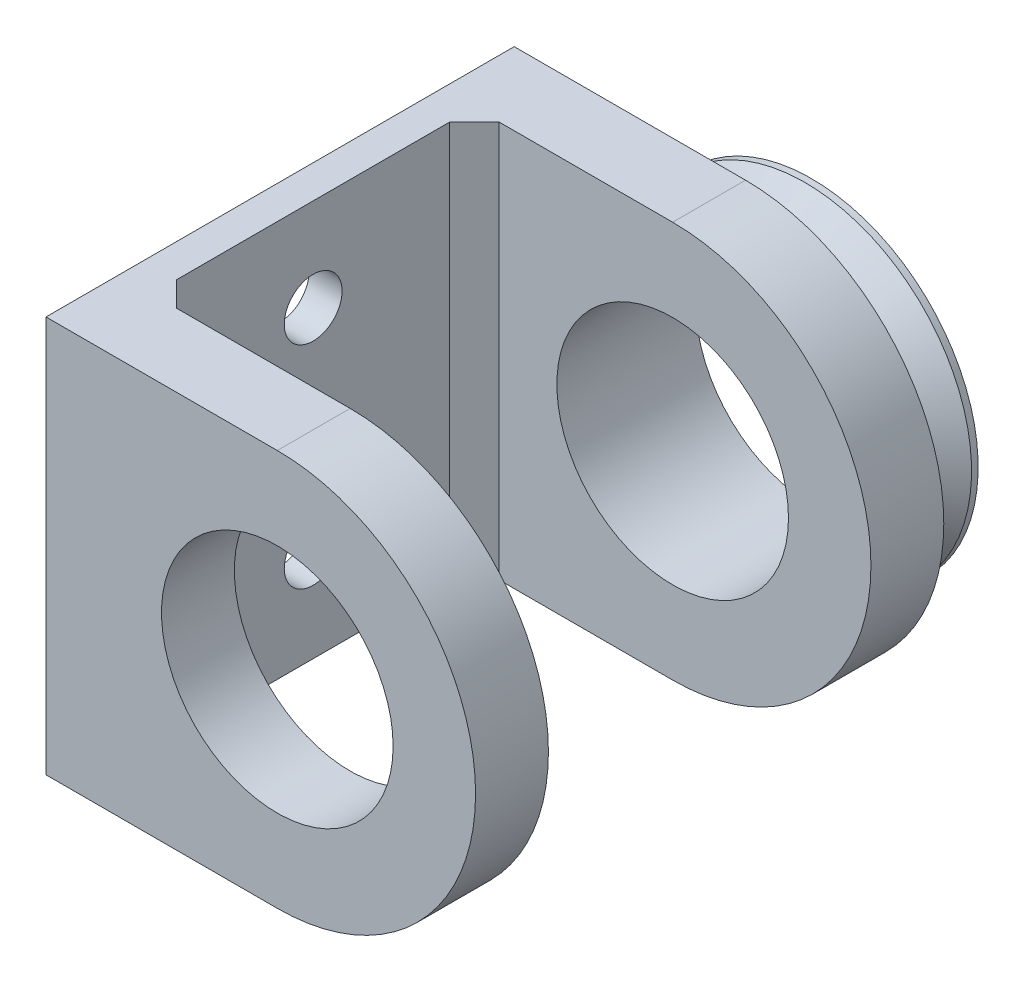
SolidWorks part; units mm, degrees
ref_plane "Front Plane" through (0, 0, 0) normal (0, 0, 1) x (1, 0, 0)
ref_plane "Top Plane" through (0, 0, 0) normal (0, 1, 0) x (1, 0, 0)
ref_plane "Right Plane" through (0, 0, 0) normal (1, 0, 0) x (0, 0, -1)
sketch "Sketch2" plane through (0, 0, 0) normal (0, 0, 1) x (1, 0, 0)
  circle A0 centre (0, 0) radius 10.9982
  dimension "D1" = 21.9964
sketch "Sketch4" plane through (0, 0, 0) normal (0, 0, 1) x (1, 0, 0)
  line L0 (-19.05, 19.05) -> (-19.05, -19.05) construction
  line L1 (-19.05, 19.05) -> (0, 19.05)
  line L2 (-19.05, -19.05) -> (0, -19.05)
  line L3 (-19.05, 19.05) -> (-22.225, 19.05)
  line L4 (-22.225, 19.05) -> (-22.225, -19.05)
  line L5 (-22.225, -19.05) -> (-19.05, -19.05)
  arc A0 (0, -19.05) -> (0, 19.05) centre (0, 0) ccw
  circle A1 centre (0, 0) radius 11.127
  dimension "D1" = 38.1
  dimension "D2" = 22.254
  dimension "D3" = 3.175
extrude "Boss-Extrude1" add sketch "Sketch4" against normal blind 7
extrude "Cut-Extrude1" [suppressed] cut sketch "Sketch2" against normal mid plane 25.4 contours A0
sketch "Sketch6" plane through (0, 0, 0) normal (0, 0, 1) x (1, 0, 0)
  line L0 (-22.225, -19.05) -> (0, -19.05) construction
  line L1 (-22.225, -19.05) -> (-19.05, -19.05)
  line L2 (-22.225, -19.05) -> (-22.225, 19.05)
  line L3 (-22.225, 19.05) -> (-19.05, 19.05)
  line L4 (-19.05, -19.05) -> (-19.05, 19.05)
  line L5 (-22.225, 19.05) -> (-22.225, -19.05) construction
  line L6 (0, 19.05) -> (-22.225, 19.05) construction
  line L7 (-19.05, 19.05) -> (-19.05, -19.05) construction
extrude "Boss-Extrude2" add sketch "Sketch6" along normal blind 15.494
chamfer "Chamfer1" distance 2.38 angle 45 1 edges at (-19.05, 0, 0)
mirror "Mirror1" about plane through (0, 0, 15.494) normal (0, 0, -1) of bodies 103
sketch "Sketch8" plane through (-19.05, 0, 0) normal (1, 0, 0) x (0, 0, -1)
  line L0 (-15.494, 19.05) -> (-15.494, -19.05) construction
  line L1 (-28.608, 19.05) -> (-2.38, 19.05) construction
  line L2 (-28.608, -19.05) -> (-2.38, -19.05) construction
  line L3 (-15.494, 0) -> (-5.0615, 0) construction
  circle A0 centre (-15.494, 10.16) radius 2.7781
  circle A1 centre (-15.494, -10.16) radius 2.7781
  dimension "D1" = 5.5562
  dimension "D2" = 10.16
extrude "Cut-Extrude2" cut sketch "Sketch8" against normal through all
sketch "Sketch9" plane through (0, 0, -7) normal (0, 0, -1) x (-1, 0, 0)
  circle A0 centre (0, 0) radius 11.127 construction
  circle A1 centre (0, 0) radius 11.127
  circle A2 centre (0, 0) radius 16.002
  dimension "D1" = 32.004
extrude "Boss-Extrude3" add sketch "Sketch9" along normal blind 3.175 separate body
chamfer "Chamfer2" distance 2.54 angle 45 1 edges at (-16.002, 0, -10.175)
mirror "Mirror2" about plane through (0, 0, -10.175) normal (0, 0, -1) of bodies 106
combine bodies "Combine1" operation type add bodies to combine 105 107
chamfer "Chamfer3" distance 2.032 angle 15 1 edges at (-16.002, 0, -7) first distance on face at (-16.002, 0, -7)
